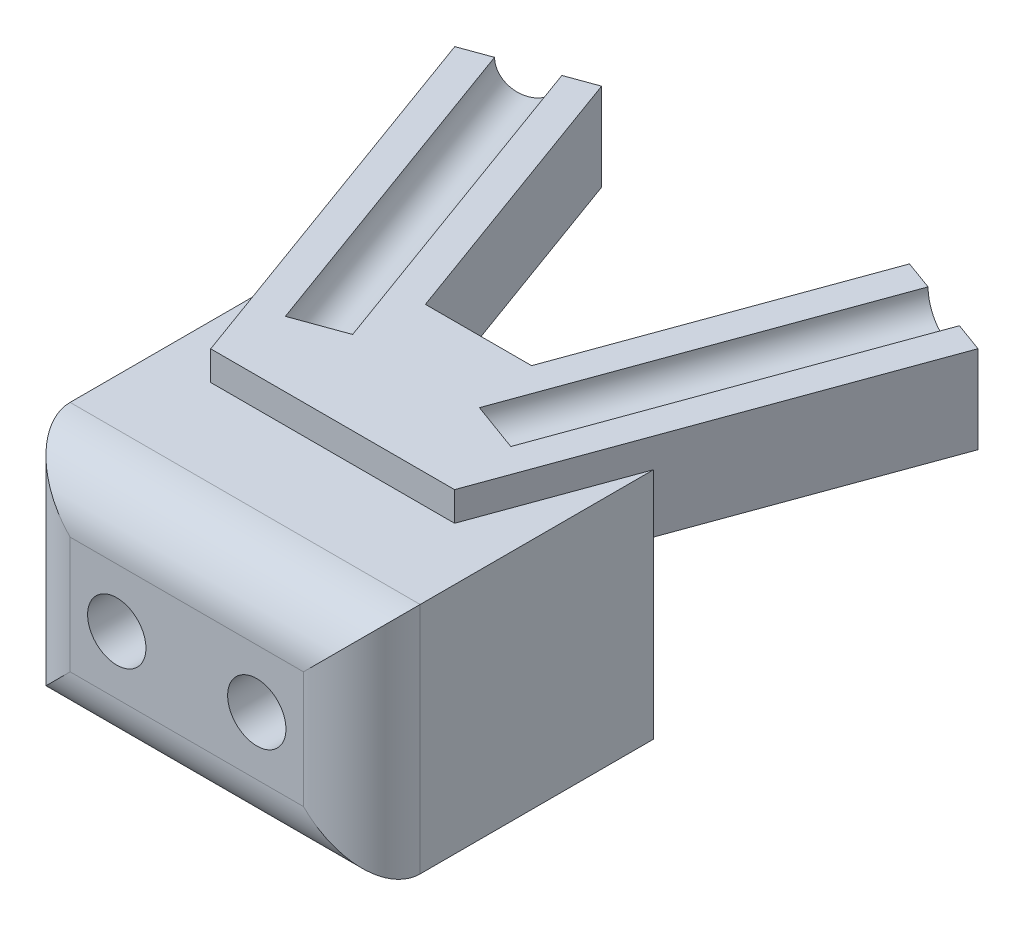
SolidWorks part; units mm, degrees
ref_plane "前视基准面" through (0, 0, 0) normal (0, 0, 1) x (1, 0, 0)
ref_plane "上视基准面" through (0, 0, 0) normal (0, 1, 0) x (1, 0, 0)
ref_plane "右视基准面" through (0, 0, 0) normal (1, 0, 0) x (0, 0, -1)
other "Configuration Table"
sketch "草图1" plane through (0, 0, 0) normal (0, 0, 1) x (1, 0, 0)
  line L1 (-3, 2) -> (3, 2)
  line L2 (-3, 2) -> (-3, -2)
  line L3 (-3, -2) -> (3, -2)
  line L4 (3, 2) -> (3, -2)
  line L5 (-3, 2) -> (3, -2) construction
  line L6 (-3, -2) -> (3, 2) construction
  point P0 (0, 0)
  dimension "D1" = 6
  dimension "D2" = 4
extrude "凸台-拉伸1" add sketch "草图1" along normal blind 5
sketch "草图2" plane through (0, 0, 0) normal (0, 0, -1) x (-1, 0, 0)
  line L0 (0, -1000) -> (0, 49000) construction
  line L1 (-1000, 0) -> (49000, 0) construction
  circle A0 centre (-1.2, 0) radius 0.5
  circle A1 centre (1.2, 0) radius 0.5
  dimension "D1" = 1
  dimension "D2" = 1.2
extrude "切除-拉伸1" cut sketch "草图2" against normal blind 5
sketch "草图3" plane through (0, 2, 0) normal (0, 1, 0) x (1, 0, 0)
  line L0 (-997, -2.5) -> (49003, -2.5) construction
  line L1 (3, -5) -> (3, 0) construction
  line L2 (0, -1000) -> (0, 49000) construction
  line L3 (0, -2.5) -> (-2.6386, 4.7496)
  line L4 (-2.0901, -2.5) -> (-4.4842, 4.0778)
  line L5 (-2.6386, 4.7496) -> (-4.4842, 4.0778)
  line L6 (-2.0901, -2.5) -> (2.0901, -2.5)
  line L7 (2.0901, -2.5) -> (4.4842, 4.0778)
  line L8 (2.6386, 4.7496) -> (4.4842, 4.0778)
  line L9 (0, -2.5) -> (2.6386, 4.7496)
  line L10 (-0.9099, 0) -> (0.9099, 0)
  line L11 (3, 0) -> (-3, 0) construction
  point P5 (3, -2.5)
  line M6 (3, 0) -> (-3, 0)
  dimension "D1" = 20
  dimension "D2" = 7
extrude "凸台-拉伸2" add sketch "草图3" along normal blind 0.5 contours L3 L9 M6 | L9 L6 L7 M6 | L4 L6 L3 M6 | L3 L5 L4 M6 | L9 L7 L8 M6 region at (-1.5, 2, 1.25) region at (1.5, 2, 1.25) region at (0, 2, 0.8333) region at (-2.7332, 2, -2.2111) region at (2.7332, 2, -2.2111)
extrude "凸台-拉伸3" add sketch "草图3<7>" against normal blind 1 contours L3 L5 L4 M6 | L9 L7 L8 M6 | L4 L6 L3 M6 | L9 L6 L7 M6 region at (-1.5, 2, 1.25) region at (1.5, 2, 1.25) region at (-2.7332, 2, -2.2111) region at (2.7332, 2, -2.2111)
sketch "草图3<7>" plane through (0, 2, 0) normal (0, 1, 0) x (1, 0, 0) same geometry as "草图3"
sketch "草图5" plane through (-1.8351, 0, -5.042) normal (-0.342, 0, -0.9397) x (-0.9397, 0, 0.342)
  line L0 (1.8371, 2.5) -> (1.8371, 1) construction
  line L1 (0.8551, 2.5) -> (2.8191, 2.5) construction
  line L2 (0.8551, 1) -> (2.8191, 1) construction
  circle A0 centre (1.8371, 2.5) radius 0.45
  dimension "D1" = 0.9
extrude "切除-拉伸2" cut sketch "草图5" against normal blind 6
mirror "镜向1" about plane through (0, 0, 0) normal (1, 0, 0) of "切除-拉伸2"
fillet "圆角1" radius 1 4 edges at (-3, 0, 5) (3, 0, 5) (0, -2, 5) (0, 2, 5)
